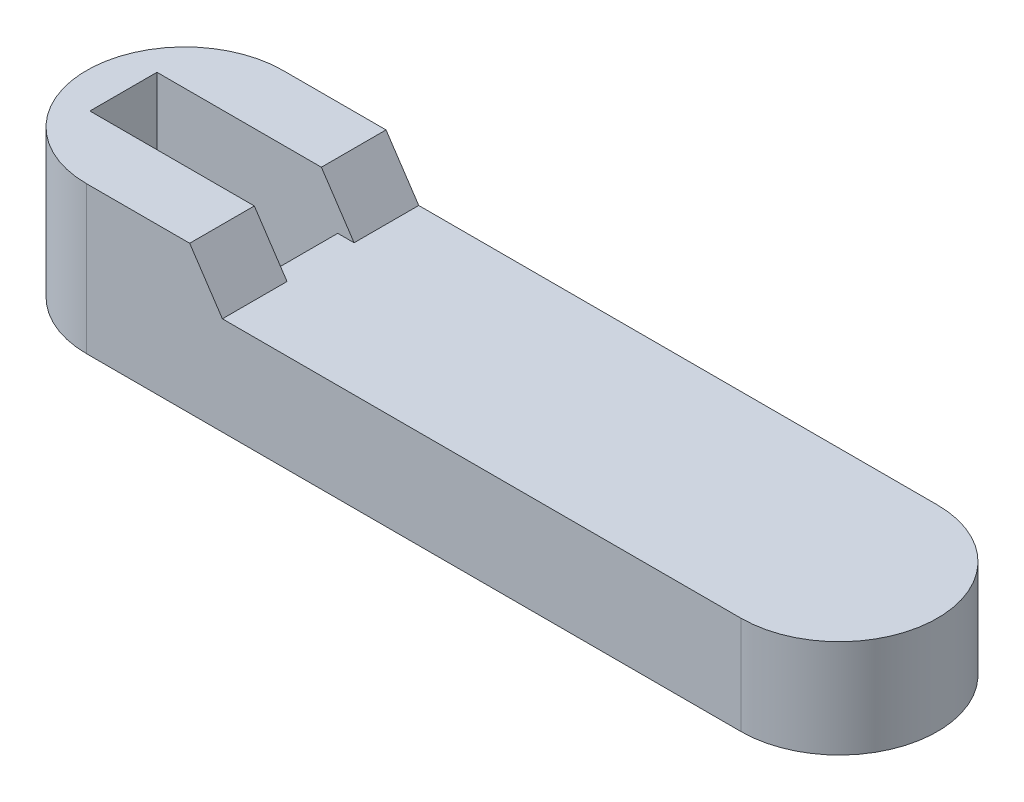
SolidWorks part; units mm, degrees
ref_plane "Front Plane" through (0, 0, 0) normal (0, 0, 1) x (1, 0, 0)
ref_plane "Top Plane" through (0, 0, 0) normal (0, 1, 0) x (1, 0, 0)
ref_plane "Right Plane" through (0, 0, 0) normal (1, 0, 0) x (0, 0, -1)
sketch "Sketch1" plane through (0, 0, 0) normal (0, 1, 0) x (1, 0, 0)
  line L0 (0, 0) -> (200, 0)
  line L1 (0, 60) -> (200, 60)
  arc A0 (0, 0) -> (0, 60) centre (0, 30) cw
  arc A1 (200, 0) -> (200, 60) centre (200, 30) ccw
  dimension "D1" = 30
  dimension "D2" = 200
extrude "Boss-Extrude1" add sketch "Sketch1" along normal blind 30
sketch "Sketch2" plane through (0, 30, 0) normal (0, 1, 0) x (1, 0, 0)
  line L0 (0, 60) -> (0, 0) construction
  circle A0 centre (0, 30) radius 7
  dimension "D1" = 14
extrude "Cut-Extrude1" cut sketch "Sketch2" against normal through all
sketch "Sketch3" plane through (0, 30, 0) normal (0, 1, 0) x (1, 0, 0)
  line L0 (0, 0) -> (0, 60) construction
  line L1 (-18.75, 40.25) -> (-18.75, 19.75)
  line L2 (-18.75, 19.75) -> (0, 19.75)
  line L3 (-18.75, 40.25) -> (0, 40.25)
  line L4 (0, 40.25) -> (36.5, 40.25)
  line L5 (36.5, 40.25) -> (36.5, 19.75)
  line L6 (36.5, 19.75) -> (0, 19.75)
  point P6 (-18.75, 30)
  point P9 (0, 30)
  dimension "D1" = 20.5
  dimension "D2" = 18.75
  dimension "D3" = 36.5
extrude "Cut-Extrude2" cut sketch "Sketch3" against normal blind 28.5
sketch "Sketch4" plane through (0, 30, 0) normal (0, 1, 0) x (1, 0, 0)
  line L0 (-18.75, 40.25) -> (41.5, 40.25)
  line L1 (41.5, 40.25) -> (41.5, 60)
  line L2 (200, 60) -> (0, 60) construction
  line L3 (41.5, 60) -> (0, 60)
  line L4 (-18.75, 40.25) -> (-18.75, 19.75)
  line L5 (-18.75, 19.75) -> (41.5, 19.75)
  line L6 (41.5, 19.75) -> (41.5, 0)
  line L7 (0, 0) -> (200, 0) construction
  line L8 (41.5, 0) -> (0, 0)
  line L9 (36.5, 19.75) -> (36.5, 40.25) construction
  line L10 (36.5, 19.75) -> (36.5, 40.25) construction
  arc A0 (0, 60) -> (0, 0) centre (0, 30) ccw
  dimension "D1" = 5
  dimension "D2" = 5
extrude "Boss-Extrude2" add sketch "Sketch4" along normal blind 15
sketch "Sketch5" plane through (0, 0, 0) normal (0, 0, 1) x (1, 0, 0)
  line L0 (31.5, 45) -> (41.5, 45)
  line L1 (0, 45) -> (41.5, 45) construction
  line L2 (41.5, 45) -> (41.5, 30)
  line L3 (41.5, 30) -> (31.5, 45)
  dimension "D1" = 10
extrude "Cut-Extrude3" cut sketch "Sketch5" against normal through all
